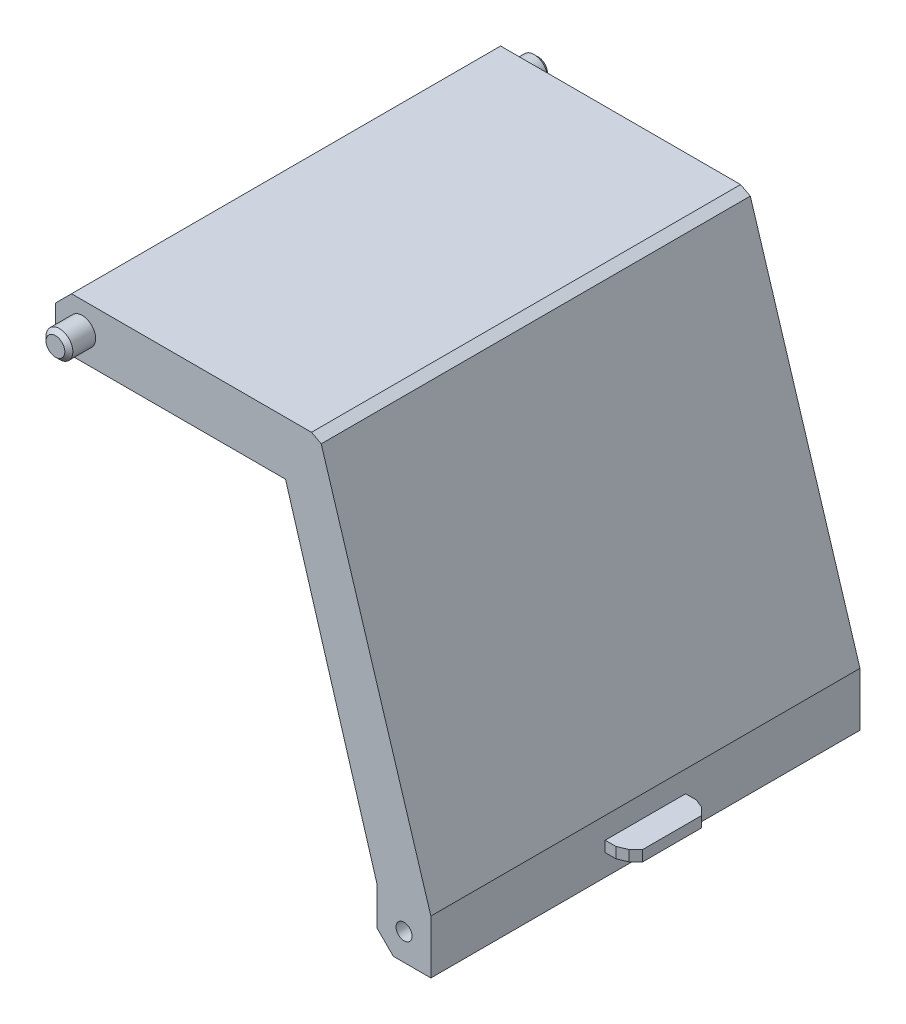
SolidWorks part; units mm, degrees
ref_plane "Front Plane" through (0, 0, 0) normal (0, 0, 1) x (1, 0, 0)
ref_plane "Top Plane" through (0, 0, 0) normal (0, 1, 0) x (1, 0, 0)
ref_plane "Right Plane" through (0, 0, 0) normal (1, 0, 0) x (0, 0, -1)
sketch "Sketch1" plane through (0, 0, 0) normal (0, 0, 1) x (1, 0, 0)
  line L0 (-5, 5) -> (-22.101, 61.9846)
  line L1 (-5, -5) -> (5, -5)
  line L2 (-5, -5) -> (-5, 5)
  line L3 (-5, 5) -> (5, 5)
  line L4 (5, -5) -> (5, 5)
  line L5 (-5, -5) -> (5, 5) construction
  line L6 (-5, 5) -> (5, -5) construction
  line L7 (5, 5) -> (-12.5931, 61.819)
  line L8 (-12.5931, 61.819) -> (-15.7407, 71.9846)
  line L13 (-15.7407, 71.9846) -> (-22.101, 71.9846)
  line L15 (-22.101, 71.9846) -> (-32.101, 71.9846)
  line L16 (-22.101, 71.9846) -> (-22.101, 61.9846)
  line L17 (-22.101, 61.9846) -> (-32.101, 61.9846)
  line L18 (-32.101, 71.9846) -> (-32.101, 61.9846)
  line L19 (-32.101, 71.9846) -> (-65.001, 71.9846)
  line L20 (-32.101, 71.9846) -> (-32.101, 61.9846)
  line L21 (-32.101, 61.9846) -> (-65.001, 61.9846)
  line L22 (-65.001, 71.9846) -> (-65.001, 61.9846)
  point P0 (0, 0)
  dimension "D1" = 10
  dimension "D2" = 10
  dimension "D3" = 10
  dimension "D4" = 32.9
extrude "Boss-Extrude1" add sketch "Sketch1" along normal blind 80 contours L15 | L8 L13 L3 L7 | L1 L4 L3 L2 | L19 L22 L21 L18 region at (0, 0, 0) region at (-9.7904, 37.4009, 0) region at (-27.101, 66.9846, 0) region at (-48.551, 66.9846, 0)
chamfer "Chamfer1" distance 3 angle 45 1 edges at (-5, -5, 40)
sketch "Sketch2" plane through (0, 0, 80) normal (0, 0, 1) x (1, 0, 0)
  line L0 (-65.001, 66.9846) -> (-60.001, 66.9846)
  line L1 (-65.001, 71.9846) -> (-65.001, 61.9846) construction
  circle A1 centre (-60.001, 66.9846) radius 2.5
extrude "Boss-Extrude2" add sketch "Sketch2" along normal blind 5 from surface contours A1 starting at face at (-18.8715, 29.5487, 80)
extrude "Boss-Extrude3" add sketch "Sketch2<2>" against normal blind 5 from surface contours A1 starting at face at (-18.8715, 29.5487, 0)
sketch "Sketch2<2>" plane through (0, 0, 80) normal (0, 0, 1) x (1, 0, 0) same geometry as "Sketch2"
chamfer "Chamfer2" distance 1 angle 45 1 edges at (-15.7407, 71.9846, 40) first distance on face at (-5.3704, 38.4923, 40)
chamfer "Chamfer3" distance 0.75 angle 45 2 edges at (-57.501, 66.9846, -5) (-57.501, 66.9846, 85)
sketch "Sketch3" plane through (5, 0, 0) normal (1, 0, 0) x (0, 0, -1)
  line L0 (-40, -5) -> (-40, 0)
  line L1 (-80, -5) -> (0, -5) construction
  line L3 (-47.5, -1) -> (-32.5, -1)
  line L4 (-47.5, -1) -> (-47.5, 1)
  line L5 (-47.5, 1) -> (-32.5, 1)
  line L6 (-32.5, -1) -> (-32.5, 1)
  line L7 (-47.5, -1) -> (-32.5, 1) construction
  line L8 (-47.5, 1) -> (-32.5, -1) construction
  dimension "D1" = 15
  dimension "D2" = 2
extrude "Boss-Extrude4" add sketch "Sketch3" along normal blind 5 contours L5 L6 L3 L4
chamfer "Chamfer4" distance 2 angle 45 2 edges at (10, 0, 32.5) (10, 0, 47.5)
chamfer "Chamfer5" distance 1 angle 22.5 2 edges at (8, 0, 32.5) (8, 0, 47.5) first distance on face at (9, 0, 33.5) first distance on face at (9, 0, 46.5)
chamfer "Chamfer6" distance 3 angle 45 2 edges at (-65.001, 71.9846, 40) (-65.001, 61.9846, 40)
sketch "Sketch4" plane through (0, 0, 80) normal (0, 0, 1) x (1, 0, 0)
  line L1 (5, -5) -> (0, -5)
  line L2 (5, -5) -> (5, 0)
  line L3 (5, 0) -> (0, 0)
  line L4 (0, -5) -> (0, 0)
  circle A0 centre (0, 0) radius 1.5
extrude "Cut-Extrude1" cut sketch "Sketch4" against normal blind 5 contours A0
extrude "Cut-Extrude2" cut sketch "Sketch4<3>" along normal blind 5 from surface contours A0 starting at face at (-57.501, 66.9846, 0)
sketch "Sketch4<3>" plane through (0, 0, 80) normal (0, 0, 1) x (1, 0, 0) same geometry as "Sketch4"
